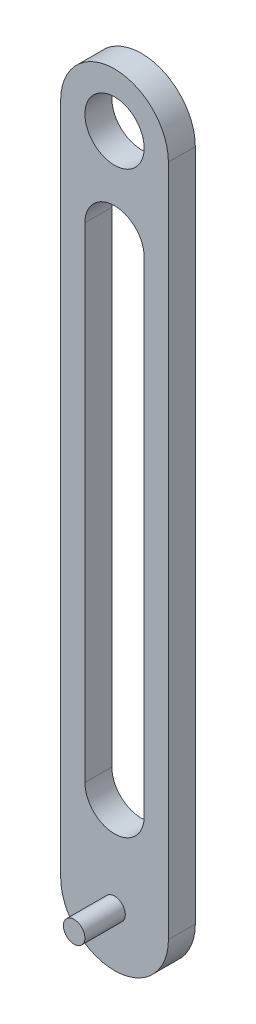
SolidWorks part; units mm, degrees
ref_plane "Front Plane" through (0, 0, 0) normal (0, 0, 1) x (1, 0, 0)
ref_plane "Top Plane" through (0, 0, 0) normal (0, 1, 0) x (1, 0, 0)
ref_plane "Right Plane" through (0, 0, 0) normal (1, 0, 0) x (0, 0, -1)
sketch "Sketch5" plane through (0, 0, 0) normal (0, 0, 1) x (1, 0, 0)
  line L2 (-20, 125) -> (-20, -125)
  line L4 (20, 125) -> (20, -125)
  line L5 (-20, 125) -> (20, -125) construction
  line L6 (-20, -125) -> (20, 125) construction
  line L7 (-11, 90) -> (-1.3622, 90)
  line L8 (-11, 90) -> (-11, -90)
  line L10 (11, 90) -> (11, -90)
  line L11 (-11, 90) -> (11, -90) construction
  line L12 (-11, -90) -> (11, 90) construction
  arc A0 (-20, 125) -> (20, 125) centre (0, 125) cw
  arc A1 (-20, -125) -> (20, -125) centre (0, -125) ccw
  arc A2 (-11, -90) -> (11, -90) centre (0, -90) ccw
  arc A3 (-11, 90) -> (11, 90) centre (0, 90) cw
  circle A4 centre (0, 125) radius 11
  circle A5 centre (0, -125) radius 4
  point P0 (0, 0)
  point P8 (0, 0)
  dimension "D5" = 22
  dimension "D6" = 8
  dimension "D7" = 20
  dimension "D8" = 11
  dimension "D1" = 250
  dimension "D2" = 40
  dimension "D3" = 22
  dimension "D4" = 180
extrude "Boss-Extrude4" add sketch "Sketch5" along normal blind 10 contours L2 A1 L4 A0 A5 A4 L8 A3 L10 A2 region at (0, 142.0725, 0)
extrude "Boss-Extrude5" add sketch "Sketch5<3>" along normal blind 25 contours A5 region at (0, -125, 0)
sketch "Sketch5<3>" plane through (0, 0, 0) normal (0, 0, 1) x (1, 0, 0) same geometry as "Sketch5"
